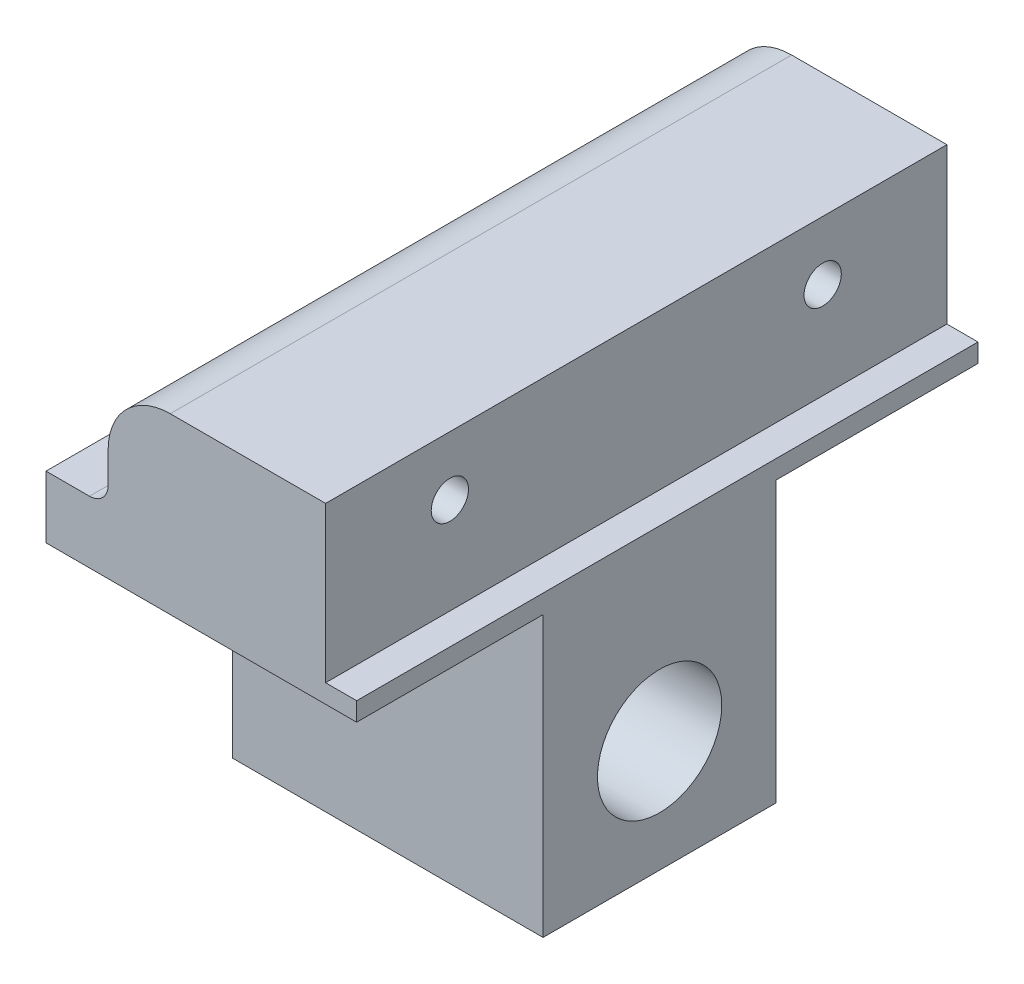
SolidWorks part; units mm, degrees
ref_plane "Front Plane" through (0, 0, 0) normal (0, 0, 1) x (1, 0, 0)
ref_plane "Top Plane" through (0, 0, 0) normal (0, 1, 0) x (1, 0, 0)
ref_plane "Right Plane" through (0, 0, 0) normal (1, 0, 0) x (0, 0, -1)
sketch "Sketch2" plane through (0, 0, 0) normal (0, 0, 1) x (1, 0, 0)
  line L1 (-10.6555, -42.3645) -> (39.3445, -42.3645)
  line L2 (39.3445, -42.3645) -> (39.3445, 2.6355)
  line L4 (39.3445, 2.6355) -> (39.3445, 5.6355)
  line L5 (39.3445, 5.6355) -> (34.3445, 5.6355)
  line L6 (34.3445, 5.6355) -> (34.3445, 30.6355)
  line L7 (34.3445, 30.6355) -> (9.3445, 30.6355)
  line L8 (-0.6555, 20.6355) -> (-0.6555, 15.6355)
  line L9 (-3.6555, 12.6355) -> (-10.6555, 12.6355)
  line L10 (-10.6555, 12.6355) -> (-10.6555, -42.3645)
  arc A0 (-0.6555, 15.6355) -> (-3.6555, 12.6355) centre (-3.6555, 15.6355) cw
  arc A1 (9.3445, 30.6355) -> (-0.6555, 20.6355) centre (9.3445, 20.6355) ccw
  point P17 (-0.6555, 30.6355)
  dimension "D8" = 3
  dimension "D9" = 10
  dimension "D1" = 5
  dimension "D2" = 50
  dimension "D3" = 35
  dimension "D7" = 25
extrude "Boss-Extrude1" add sketch "Sketch2" along normal blind 100 contours L7 A1 L8 A0 L9 L10 L1 L2 L4 L5 L6
sketch "Sketch3" plane through (39.3445, 0, 0) normal (1, 0, 0) x (0, 0, -1)
  line L0 (-100, 2.6355) -> (0, 2.6355)
  line L1 (-100, 5.6355) -> (0, 5.6355) construction
  line L2 (-100, -42.3645) -> (-100, 5.6355) construction
  line L3 (0, -42.3645) -> (0, 5.6355) construction
  line L4 (-50, 2.6355) -> (-50, -42.3645) construction
  line L5 (-100, -42.3645) -> (0, -42.3645) construction
  line L6 (-50, -42.3645) -> (-32.4868, -42.3645)
  line L7 (-32.4868, -42.3645) -> (-32.4868, 2.6355)
  line L8 (-32.4868, -42.3645) -> (0, -42.3645)
  line L9 (0, -42.3645) -> (0, 2.6355)
  dimension "D1" = 3
extrude "Cut-Extrude5" cut sketch "Sketch3" against normal through all contours L7 L1 L0 region at (39.3445, -19.8645, 16.2434)
sketch "Sketch7" plane through (39.3445, 0, 0) normal (1, 0, 0) x (0, 0, -1)
  line L0 (-50, 5.6355) -> (-50, -42.3645) construction
  line L1 (-100, 5.6355) -> (0, 5.6355) construction
  line L2 (-100, -42.3645) -> (-32.4868, -42.3645) construction
  line L3 (-70, 2.6355) -> (-70, -42.3645)
  line L5 (-70, 2.6355) -> (-100, 2.6355)
  line L6 (-100, -42.3645) -> (-100, 5.6355) construction
  line L7 (-100, -42.3645) -> (-70, -42.3645)
  line L9 (-100, 2.6355) -> (-100, -42.3645)
extrude "Cut-Extrude7" cut sketch "Sketch7" against normal through all
sketch "Sketch8" plane through (39.3445, 0, 0) normal (1, 0, 0) x (0, 0, -1)
  line L0 (-51.2434, -42.3645) -> (-51.2434, 5.6355) construction
  line L1 (-70, -42.3645) -> (-32.4868, -42.3645) construction
  line L2 (-100, 5.6355) -> (0, 5.6355) construction
  circle A0 centre (-51.2434, -24.3645) radius 10
  dimension "D2" = 20
  dimension "D1" = 18
extrude "Cut-Extrude8" cut sketch "Sketch8" against normal through all
sketch "Sketch9" plane through (34.3445, 0, 0) normal (1, 0, 0) x (0, 0, -1)
  line L0 (-50, 5.6355) -> (-50, 30.6355) construction
  line L1 (-100, 5.6355) -> (0, 5.6355) construction
  line L2 (-100, 30.6355) -> (0, 30.6355) construction
  circle A0 centre (-20, 21.1355) radius 2.5
  circle A1 centre (-80, 21.1355) radius 2.5
  point P6 (-20, 21.1355)
  dimension "D3" = 5
  dimension "D1" = 15.5
  dimension "D2" = 30
extrude "Cut-Extrude9" cut sketch "Sketch9" against normal blind 13
sketch "Sketch10" plane through (34.3445, 0, 0) normal (1, 0, 0) x (0, 0, -1)
  line L0 (-50, 5.6355) -> (-50, 30.6355) construction
  line L1 (-100, 5.6355) -> (0, 5.6355) construction
  line L2 (-100, 30.6355) -> (0, 30.6355) construction
  circle A0 centre (-20, 21.1355) radius 3
  circle A1 centre (-80, 21.1355) radius 3
  dimension "D1" = 6
extrude "Cut-Extrude10" cut sketch "Sketch10" against normal blind 10
fillet "Fillet1" radius 1 1 edges at (24.3445, 21.1355, 17)
fillet "Fillet2" radius 1 1 edges at (24.3445, 21.1355, 83)
sketch "Sketch11" plane through (0, -42.3645, 0) normal (0, -1, 0) x (1, 0, 0)
  line L0 (-10.6555, 51.2434) -> (39.3445, 51.2434) construction
  line L1 (-10.6555, 70) -> (-10.6555, 32.4868) construction
  line L2 (39.3445, 70) -> (39.3445, 32.4868) construction
  circle A0 centre (14.3445, 63.2434) radius 2.5
  circle A1 centre (14.3445, 39.2434) radius 2.5
  point P6 (14.3445, 63.2434)
  dimension "D3" = 5
  dimension "D1" = 10
  dimension "D2" = 25
extrude "Cut-Extrude11" cut sketch "Sketch11" against normal blind 13
sketch "Sketch12" plane through (0, -42.3645, 0) normal (0, -1, 0) x (1, 0, 0)
  line L0 (-10.6555, 51.2434) -> (39.3445, 51.2434) construction
  line L1 (-10.6555, 70) -> (-10.6555, 32.4868) construction
  line L2 (39.3445, 70) -> (39.3445, 32.4868) construction
  circle A0 centre (14.3445, 63.2434) radius 3
  circle A1 centre (14.3445, 39.2434) radius 3
  dimension "D1" = 6
extrude "Cut-Extrude12" cut sketch "Sketch12" against normal blind 10
fillet "Fillet3" radius 1 2 edges at (14.3445, -32.3645, 42.2434) (14.3445, -32.3645, 60.2434)
